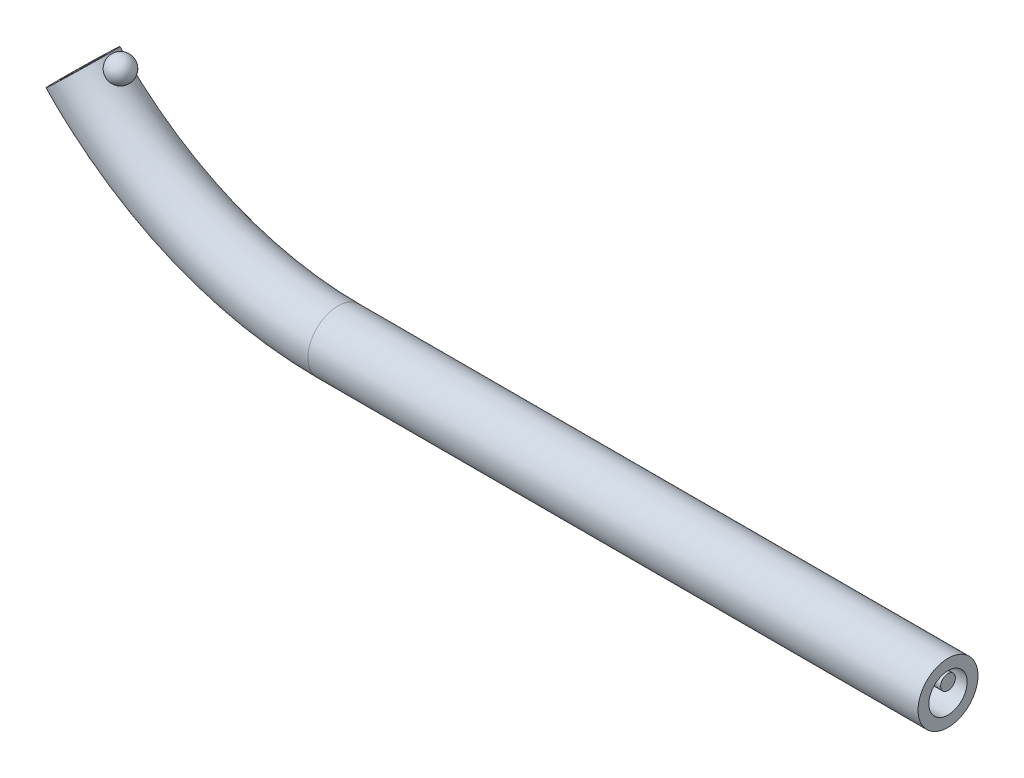
SolidWorks part; units mm, degrees
ref_plane "Front Plane" through (0, 0, 0) normal (0, 0, 1) x (1, 0, 0)
ref_plane "Top Plane" through (0, 0, 0) normal (0, 1, 0) x (1, 0, 0)
ref_plane "Right Plane" through (0, 0, 0) normal (1, 0, 0) x (0, 0, -1)
ref_axis "Axis1" through (-88.99, 0, 0) along (1, 0, 0)
sketch "Sketch4" plane through (0, 0, 0) normal (0, 0, 1) x (1, 0, 0)
  line L0 (-218.053, 283.5718) -> (61.923, 683.419) construction
  line L1 (-68.365, 0) -> (-65.9542, 0)
  arc A0 (-68.365, 0) -> (-73.5499, 2.2253) centre (-68.365, 7.1532) cw
  point P2 (-73.5499, 2.2253)
  point P3 (-68.365, 0)
sketch "Sketch1" plane through (0, 0, 0) normal (1, 0, 0) x (0, 0, -1)
  circle A0 centre (0, 0) radius 0.61
  circle A1 centre (0, 0) radius 0.39
  dimension "D1" = 1.22
  dimension "D2" = 0.22
extrude "Boss-Extrude1" [suppressed] add sketch "Sketch1" along normal blind 10
ref_plane "Plane1" through (-65.9542, 0, 0) normal (1, 0, 0) x (0, 0, -1)
sketch "Sketch5" plane through (-65.9542, 0, 0) normal (1, 0, 0) x (0, 0, -1)
  circle A0 centre (0, 0) radius 0.61
  circle A1 centre (0, 0) radius 0.39
  dimension "D1" = 1.22
  dimension "D2" = 0.22
sweep "Sweep2" add profiles "Sketch5" path "Sketch4"
extrude "Boss-Extrude2" add sketch "Sketch5<2>" along normal blind 10
sketch "Sketch5<2>" plane through (-65.9542, 0, 0) normal (1, 0, 0) x (0, 0, -1) same geometry as "Sketch5"
sketch "Sketch6" plane through (0, 0, 0) normal (0, 0, 1) x (1, 0, 0)
  line L0 (-72.7874, 2.8286) -> (-72.7874, 2.3286) construction
  line L1 (-72.9491, 2.3879) -> (-72.6257, 2.7693)
  circle A0 centre (-72.7874, 2.5786) radius 0.25 construction
  arc A1 (-72.9491, 2.3879) -> (-72.6257, 2.7693) centre (-72.7874, 2.5786) ccw
  dimension "D1" = 0.5
revolve "Revolve2" add sketch "Sketch6" angle 360 about L1
sketch "Sketch7" plane through (0, 0, 0) normal (0, 0, 1) x (1, 0, 0)
  line L0 (-68.365, -0.61) -> (-55.9542, -0.61) construction
  line L1 (-68.365, -0.61) -> (-55.9542, -0.61) construction
  line L2 (-68.365, 0.19) -> (-55.9542, 0.19)
  arc A1 (-73.9921, 1.805) -> (-68.365, -0.61) centre (-68.365, 7.1532) ccw construction
  arc A2 (-73.9921, 1.805) -> (-68.365, -0.61) centre (-68.365, 7.1532) ccw construction
  arc A3 (-73.4122, 2.3562) -> (-68.365, 0.19) centre (-68.365, 7.1532) ccw
  dimension "D1" = 0.8
sketch "Sketch8" plane through (-36.0182, 37.8966, 0) normal (-0.6889, 0.7248, 0) x (0.7248, 0.6889, 0)
  circle A0 centre (-51.5891, 0) radius 0.15
  point P0 (-51.5891, 0)
  dimension "D1" = 0.3
sweep "Sweep3" add profiles "Sketch8" path "Sketch7"
